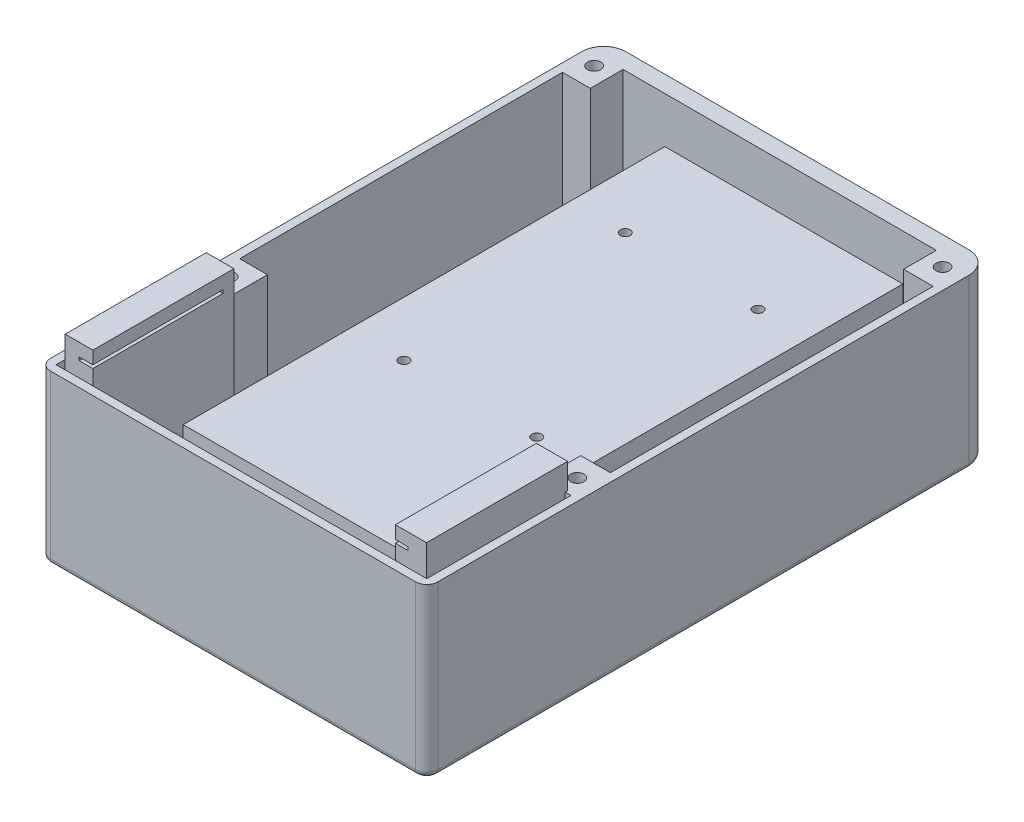
SolidWorks part; units mm, degrees
ref_plane "Front Plane" through (0, 0, 0) normal (0, 0, 1) x (1, 0, 0)
ref_plane "Top Plane" through (0, 0, 0) normal (0, 1, 0) x (1, 0, 0)
ref_plane "Right Plane" through (0, 0, 0) normal (1, 0, 0) x (0, 0, -1)
sketch "Sketch1" plane through (0, 0, 0) normal (0, 1, 0) x (1, 0, 0)
  line L0 (0, 0) -> (70, 0)
  line L1 (70, 0) -> (70, 102)
  line L2 (70, 102) -> (0, 102)
  line L3 (0, 102) -> (0, 0)
extrude "Boss-Extrude1" add sketch "Sketch1" along normal blind 2
sketch "Sketch5" plane through (0, 0, 0) normal (0, 1, 0) x (1, 0, 0)
  line L0 (15.98, 97.0561) -> (59, 97.0561)
  line L1 (59, 97.0561) -> (59, 10)
  line L2 (59, 10) -> (15.98, 10)
  line L3 (15.98, 10) -> (15.98, 97.0561)
extrude "Boss-Extrude3" add sketch "Sketch5" along normal blind 24
sketch "Sketch8" plane through (0, 0, 0) normal (0, 1, 0) x (1, 0, 0)
  line L0 (58.8817, 98.35) -> (17.7555, 98.35)
  line L1 (17.7555, 98.35) -> (17.7555, 10)
  line L2 (17.7555, 10) -> (58.8817, 10)
  line L3 (58.8817, 10) -> (58.8817, 98.35)
extrude "Cut-Extrude1" cut sketch "Sketch8" along normal blind 21.6
sketch "Sketch9" plane through (0, 0, 0) normal (1, 0, 0) x (0, 0, -1)
  line L0 (0, 0) -> (0, 30.3906)
  line L1 (102, 0) -> (102, 30.3906)
  line L2 (102, 30.3906) -> (0, 30.3906)
  line L3 (0, 0) -> (102, 0)
extrude "Boss-Extrude4" add sketch "Sketch9" along normal blind 1.5
sketch "Sketch10" plane through (0, 0, 0) normal (1, 0, 0) x (0, 0, -1)
  line L0 (102, 0) -> (102, 30.3906)
  line L1 (102, 30.3906) -> (98.9646, 30.3906)
  line L2 (102, 30.3906) -> (0, 30.3906) construction
  line L3 (98.9646, 30.3906) -> (98.9646, 0)
  line L4 (102, 0) -> (0, 0) construction
  line L5 (98.9646, 0) -> (102, 0)
extrude "Boss-Extrude5" add sketch "Sketch10" along normal blind 70
sketch "Sketch12" plane through (0, 0, 0) normal (0, 0, 1) x (1, 0, 0)
  line L0 (0, 0) -> (70, 0)
  line L1 (0, 0) -> (0, 30.3906)
  line L2 (0, 30.3906) -> (70, 30.3906)
  line L3 (70, 30.3906) -> (70, 0)
extrude "Boss-Extrude6" add sketch "Sketch12" against normal blind 1.5
sketch "Sketch13" plane through (0, 0, 0) normal (0, 0, 1) x (1, 0, 0)
  line L0 (70, 0) -> (68.5, 0)
  line L1 (0, 0) -> (70, 0) construction
  line L2 (68.5, 0) -> (68.5, 30.3906)
  line L3 (70, 30.3906) -> (0, 30.3906) construction
  line L4 (68.5, 30.3906) -> (70, 30.3906)
  line L5 (70, 30.3906) -> (70, 0)
extrude "Boss-Extrude7" add sketch "Sketch13" against normal blind 102
sketch "Sketch14" plane through (0, 0, 0) normal (0, 1, 0) x (1, 0, 0)
  line L0 (70, 0) -> (70, 102) construction
  line L1 (6.522, 27.5719) -> (0.6991, 27.5719)
  line L2 (6.522, 27.5719) -> (6.522, 34.6883)
  line L3 (6.522, 34.6883) -> (0.6991, 34.6883)
  line L4 (0.6991, 27.5719) -> (0.6991, 34.6883)
  line L5 (6.522, 93.0438) -> (0, 93.0438)
  line L6 (6.522, 93.0438) -> (6.522, 102)
  line L7 (6.522, 102) -> (0, 102)
  line L8 (0, 93.0438) -> (0, 102)
  line L9 (70, 93.04) -> (63.1524, 93.04)
  line L10 (70, 93.04) -> (70, 102)
  line L11 (70, 102) -> (63.1524, 102)
  line L12 (63.1524, 93.04) -> (63.1524, 102)
  line L13 (70, 102) -> (0, 102) construction
  line L19 (63.1524, 27.5719) -> (70, 27.5719)
  line L20 (63.1524, 27.5719) -> (63.1524, 34.6883)
  line L21 (63.1524, 34.6883) -> (70, 34.6883)
  line L22 (70, 27.5719) -> (70, 34.6883)
extrude "Boss-Extrude8" add sketch "Sketch14" along normal through all
hole_wizard "CSK for M2 Flat Head Machine Screw2" positions "Sketch17" profile "Sketch18" countersink size "M2" standard "ANSI Metric" end condition through all
sketch "Sketch17" plane through (0, 0, 0) normal (0, -1, 0) x (-1, 0, 0)
  point P0 (-3.3375, 96.9138)
  point P2 (-66.3314, 96.9138)
  point P4 (-66.3314, 30.8877)
  point P6 (-3.3375, 30.8877)
  point P7 (-3.3375, 95.3761)
  point P8 (-3.3375, 96.4746)
  point P9 (-66.3314, 96.4746)
  point P10 (-3.3375, 96.4746)
  point P11 (-3.3375, 96.4746)
  point P12 (-3.3375, 96.9138)
  point P13 (-66.3314, 96.9138)
sketch "Sketch18" plane through (3.3375, 0, -96.9138) normal (1, 0, 0) x (0, 0, -1)
  line L0 (0, 0) -> (0, 30.3906)
  line L1 (0, 30.3906) -> (1.2, 30.3906)
  line L2 (1.2, 30.3906) -> (1.2, 1)
  line L3 (1.2, 1) -> (2.2, 0)
  line L5 (2.2, 0) -> (0, 0)
  line L6 (-1.2, 1) -> (-2.2, 0) construction
  line L11 (0, -6.35) -> (0, 107.95) construction
  dimension "Thru Hole Dia." = 2.4
  dimension "Thru Hole Depth" = 30.3906
  dimension "Near C'Sink Dia." = 4.4
  dimension "Near C'Sink Angle" = 90
fillet "Fillet3" radius 4 2 edges at (0, 15.1953, -102) (70, 15.1953, -102)
fillet "Fillet4" radius 1 7 edges at (1.1716, 0, -100.8284) (35, 0, -102) (68.8284, 0, -100.8284) (70, 0, -49) (34.8372, 2, -98.9646) (0, 0, -49) (35, 0, 0)
hole_wizard "CSK for M1.6 Cross Recess Flat Head Screw1" positions "Sketch23" profile "Sketch24" countersink size "M1.6" standard "IS" end condition through all
sketch "Sketch23" plane through (0, 21.6, 0) normal (0, -1, 0) x (-1, 0, 0)
  point P0 (-25.8817, 40)
  point P2 (-49.8817, 40)
  point P3 (-25.8817, 80)
  point P5 (-49.8817, 80)
  point P11 (-25.8817, 40)
  point P13 (-49.8817, 40)
  point P15 (-51.021, 80)
  point P16 (-49.8817, 80)
  point P18 (-25.8817, 80)
sketch "Sketch24" plane through (25.8817, 21.6, -40) normal (1, 0, 0) x (0, 0, -1)
  line L0 (0, 0) -> (0, 8.7906)
  line L1 (0, 8.7906) -> (0.9, 8.7906)
  line L2 (0.9, 8.7906) -> (0.9, 0.9)
  line L3 (0.9, 0.9) -> (1.8, 0)
  line L5 (1.8, 0) -> (0, 0)
  line L6 (-0.9, 0.9) -> (-1.8, 0) construction
  line L11 (0, -6.35) -> (0, 107.95) construction
  dimension "Thru Hole Dia." = 1.8
  dimension "Thru Hole Depth" = 8.7906
  dimension "Near C'Sink Dia." = 3.6
  dimension "Near C'Sink Angle" = 90
sketch "Sketch25" plane through (0, 0, 0) normal (0, 1, 0) x (1, 0, 0)
  line L1 (2.1492, 2.5) -> (7.1518, 2.5)
  line L2 (2.1492, 2.5) -> (2.1492, 28)
  line L3 (2.1492, 28) -> (7.1518, 28)
  line L4 (7.1518, 2.5) -> (7.1518, 28)
  line L5 (61.8278, 2.5) -> (67.4571, 2.5)
  line L6 (61.8278, 2.5) -> (61.8278, 28)
  line L7 (61.8278, 28) -> (67.4571, 28)
  line L8 (67.4571, 2.5) -> (67.4571, 28)
extrude "Boss-Extrude11" add sketch "Sketch25" along normal blind 35
fillet "Fillet5" radius 2 4 edges at (0.2929, 0.2929, -0.2929) (69.7071, 0.2929, -0.2929) (70, 15.6953, 0) (0, 15.6953, 0)
sketch "Sketch43" plane through (0, 0, 0) normal (0, 0, 1) x (1, 0, 0)
  line L1 (4.6711, 32.6923) -> (64.0801, 32.6923)
  line L2 (4.6711, 32.6923) -> (4.6711, 32.1175)
  line L3 (4.6711, 32.1175) -> (64.0801, 32.1175)
  line L4 (64.0801, 32.6923) -> (64.0801, 32.1175)
extrude "Cut-Extrude6" cut sketch "Sketch43" against normal blind 26
